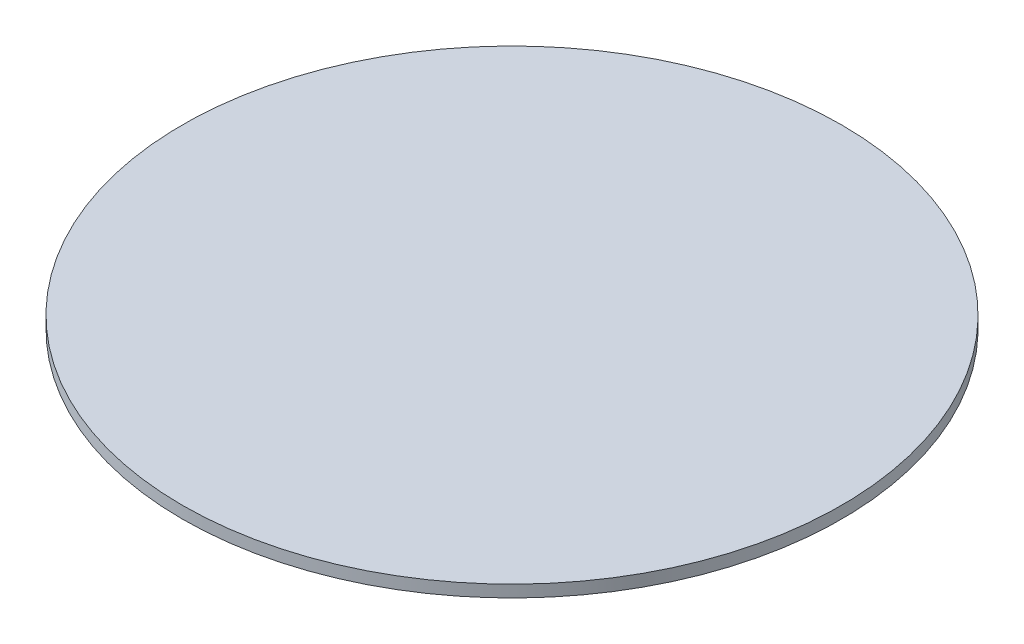
SolidWorks part; units mm, degrees
ref_plane "Plano frontal" through (0, 0, 0) normal (0, 0, 1) x (1, 0, 0)
ref_plane "Plano superior" through (0, 0, 0) normal (0, 1, 0) x (1, 0, 0)
ref_plane "Plano direito" through (0, 0, 0) normal (1, 0, 0) x (0, 0, -1)
sketch "Esboço1" plane through (0, 0, 0) normal (0, 1, 0) x (1, 0, 0)
  circle A0 centre (0, 0) radius 110
extrude "Ressalto-extrusão1" add sketch "Esboço1" along normal blind 4
